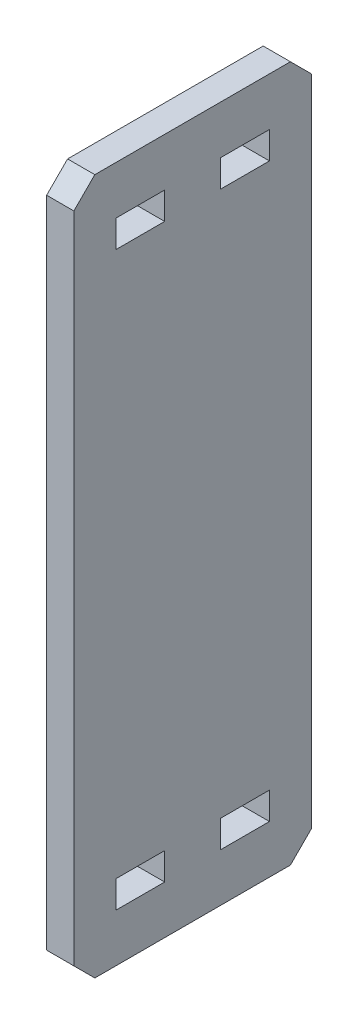
SolidWorks part; units mm, degrees
ref_plane "Front" through (0, 0, 0) normal (0, 0, 1) x (1, 0, 0)
ref_plane "Top" through (0, 0, 0) normal (0, 1, 0) x (1, 0, 0)
ref_plane "Right" through (0, 0, 0) normal (1, 0, 0) x (0, 0, -1)
ref_axis "side-side" through (80.9, 0, 0) along (-1, 0, 0)
ref_axis "up-down" through (0, 50, 0) along (0, -1, 0)
ref_axis "front-back" through (0, 0, -80.9) along (0, 0, 1)
sketch "Sketch1" plane through (0, 0, 0) normal (1, 0, 0) x (0, 0, -1)
  line L1 (-89.4373, 63.246) -> (-132.6173, 63.246)
  line L2 (-89.4373, 63.246) -> (-89.4373, -63.246)
  line L3 (-89.4373, -63.246) -> (-132.6173, -63.246)
  line L4 (-132.6173, 63.246) -> (-132.6173, -63.246)
  line L9 (-97.0573, 54.483) -> (-105.9473, 54.483)
  line L10 (-97.0573, 54.483) -> (-97.0573, 49.53)
  line L11 (-97.0573, 49.53) -> (-105.9473, 49.53)
  line L12 (-124.9973, 54.483) -> (-124.9973, 49.53)
  line L13 (-97.0573, -49.53) -> (-105.9473, -49.53)
  line L14 (-97.0573, -49.53) -> (-97.0573, -54.483)
  line L15 (-97.0573, -54.483) -> (-105.9473, -54.483)
  line L16 (-124.9973, -49.53) -> (-124.9973, -54.483)
  line L18 (-105.9473, 54.483) -> (-105.9473, 49.53) construction
  line L19 (-105.9473, 54.483) -> (-105.9473, 49.53)
  line L20 (-116.1073, 54.483) -> (-116.1073, 49.53) construction
  line L21 (-116.1073, 54.483) -> (-116.1073, 49.53)
  line L22 (-116.1073, 54.483) -> (-124.9973, 54.483)
  line L23 (-116.1073, 49.53) -> (-124.9973, 49.53)
  line L24 (-116.1073, -49.53) -> (-116.1073, -54.483) construction
  line L25 (-116.1073, -49.53) -> (-116.1073, -54.483)
  line L26 (-105.9473, -49.53) -> (-105.9473, -54.483) construction
  line L27 (-105.9473, -49.53) -> (-105.9473, -54.483)
  line L28 (-116.1073, -49.53) -> (-124.9973, -49.53)
  line L29 (-116.1073, -54.483) -> (-124.9973, -54.483)
extrude "Boss-Extrude1" add sketch "Sketch1" along normal mid plane 4.953
chamfer "Chamfer1" distance 3.81 angle 45 4 edges at (0, -63.246, 89.4373) (0, -63.246, 132.6173) (0, 63.246, 89.4373) (0, 63.246, 132.6173)
